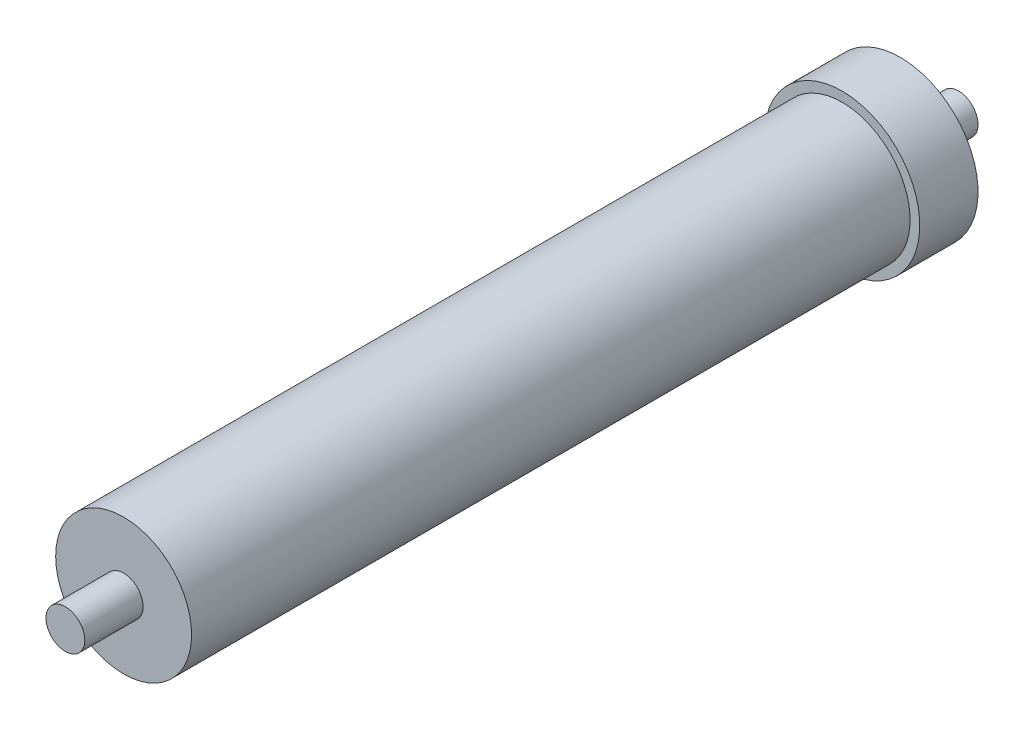
SolidWorks part; units mm, degrees
material "Сталь ШХ15 ГОСТ 801-78"
ref_plane "Plane1" through (0, 0, 0) normal (0, 0, 1) x (1, 0, 0)
ref_plane "Plane2" through (0, 0, 0) normal (0, 1, 0) x (1, 0, 0)
ref_plane "Plane3" through (0, 0, 0) normal (1, 0, 0) x (0, 0, -1)
sketch "Эскиз1" plane through (0, 0, 0) normal (0, 0, 1) x (1, 0, 0)
  circle A0 centre (0, 0) radius 3.5
  dimension "D1" = 7
extrude "Бобышка-Вытянуть1" add sketch "Эскиз1" along normal blind 40 contours A0
sketch "Эскиз2" plane through (0, 0, 40) normal (0, 0, 1) x (1, 0, 0)
  circle A0 centre (0, 0) radius 1
  dimension "D1" = 2
extrude "Бобышка-Вытянуть2" add sketch "Эскиз2" along normal blind 3 contours A0
sketch "Эскиз4" plane through (0, 0, 0) normal (0, 0, -1) x (-1, 0, 0)
  circle A0 centre (0, 0) radius 1
  dimension "D1" = 2
extrude "Бобышка-Вытянуть3" add sketch "Эскиз4" along normal up to surface (3 mm away)
sketch "Эскиз6" plane through (0, 0, 0) normal (0, 0, -1) x (-1, 0, 0)
  circle A0 centre (0, 0) radius 4
  dimension "D1" = 8
extrude "Бобышка-Вытянуть5" add sketch "Эскиз6" against normal blind 3
